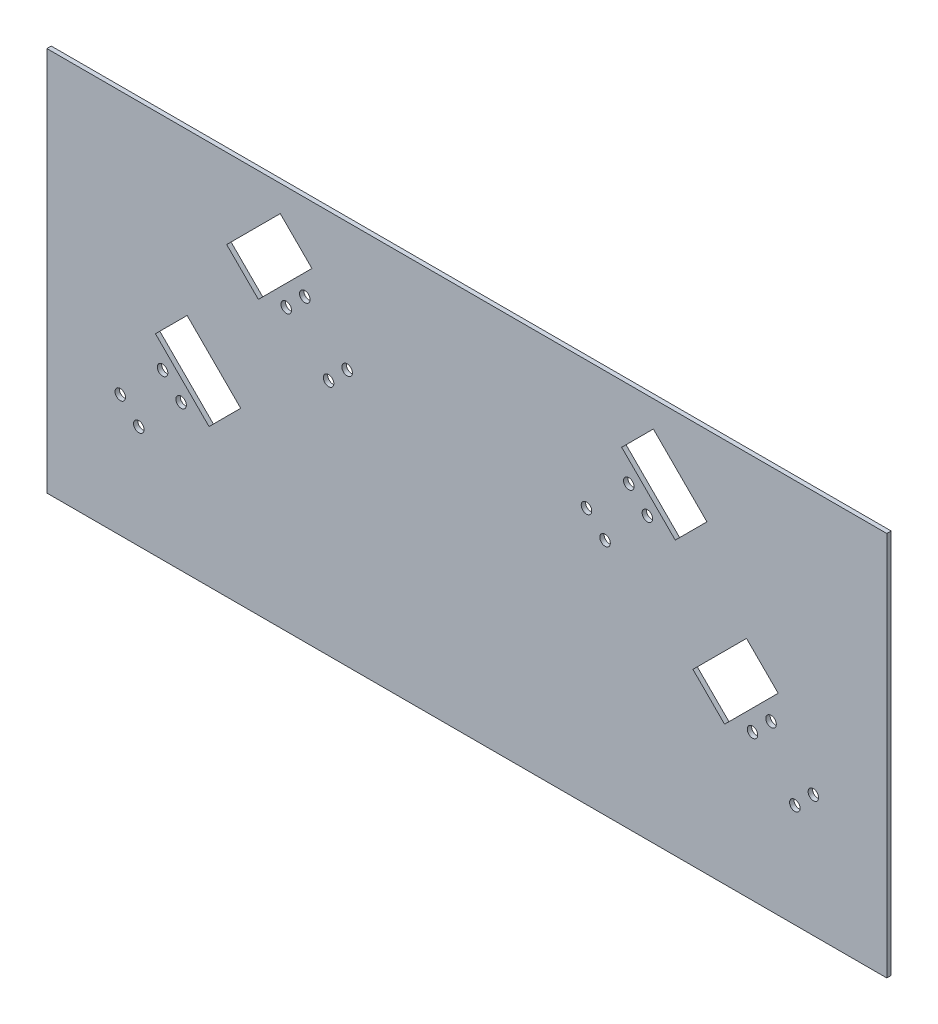
SolidWorks part; units mm, degrees
ref_plane "Front" through (0, 0, 0) normal (0, 0, 1) x (1, 0, 0)
ref_plane "Top" through (0, 0, 0) normal (0, 1, 0) x (1, 0, 0)
ref_plane "Right" through (0, 0, 0) normal (1, 0, 0) x (0, 0, -1)
sketch "Sketch1" plane through (0, 0, 0) normal (0, 0, 1) x (1, 0, 0)
  line L0 (0, -42.031) -> (0, 0) construction
  line L1 (-101.6, 0) -> (101.6, 0)
  line L13 (-206.5277, -159.2953) -> (-183.5467, -136.3143) construction
  line L31 (-304.8, 0) -> (304.8, 0)
  line L32 (-304.8, 0) -> (-304.8, -279.4)
  line L33 (-304.8, -279.4) -> (304.8, -279.4)
  line L34 (304.8, 0) -> (304.8, -279.4)
  line L51 (-116.131, -50.2511) -> (-47.7374, -118.6447)
  line L52 (-116.131, -50.2511) -> (-143.0718, -77.1919)
  line L53 (-143.0718, -77.1919) -> (-74.6782, -145.5855)
  line L54 (-47.7374, -118.6447) -> (-74.6782, -145.5855)
  line L55 (-154.8274, -38.4954) -> (-131.8465, -61.4764) construction
  line L56 (-129.6014, -63.7215) -> (-61.2078, -132.1151) construction
  line L57 (-195.3024, -175.0107) -> (-222.2432, -148.07)
  line L58 (-195.3024, -175.0107) -> (-263.696, -243.4044)
  line L59 (-263.696, -243.4044) -> (-290.6368, -216.4636)
  line L60 (-222.2432, -148.07) -> (-290.6368, -216.4636)
  line L61 (-208.7728, -161.5403) -> (-277.1664, -229.934) construction
  line L62 (-263.5523, -189.3791) -> (-235.6776, -217.2539)
  line L63 (-242.8977, -168.7245) -> (-215.957, -195.6653) construction
  line L69 (-101.7626, -118.501) -> (-74.8218, -91.5603)
  line L70 (-95.4764, -70.9057) -> (-122.4172, -97.8464) construction
  line L71 (95.4764, -70.9057) -> (122.4172, -97.8464) construction
  line L72 (242.8977, -168.7245) -> (215.957, -195.6653) construction
  line L73 (208.7728, -161.5403) -> (277.1664, -229.934) construction
  line L74 (129.6014, -63.7215) -> (61.2078, -132.1151) construction
  line L75 (154.8274, -38.4954) -> (131.8465, -61.4764) construction
  line L76 (206.5277, -159.2953) -> (183.5467, -136.3143) construction
  line L77 (101.7626, -118.501) -> (74.8218, -91.5603)
  line L78 (263.5523, -189.3791) -> (235.6776, -217.2539)
  line L79 (222.2432, -148.07) -> (290.6368, -216.4636)
  line L80 (263.696, -243.4044) -> (290.6368, -216.4636)
  line L81 (195.3024, -175.0107) -> (263.696, -243.4044)
  line L82 (195.3024, -175.0107) -> (222.2432, -148.07)
  line L83 (47.7374, -118.6447) -> (74.6782, -145.5855)
  line L84 (143.0718, -77.1919) -> (74.6782, -145.5855)
  line L85 (116.131, -50.2511) -> (143.0718, -77.1919)
  line L86 (116.131, -50.2511) -> (47.7374, -118.6447)
  circle A0 centre (-220.8063, -160.1035) radius 3.81
  circle A1 centre (-207.3359, -173.5739) radius 3.81
  circle A2 centre (-238.0484, -204.2864) radius 3.81
  circle A3 centre (-251.5188, -190.816) radius 3.81
  circle A4 centre (-131.0382, -75.755) radius 3.8222
  circle A5 centre (-117.5679, -62.2846) radius 3.8222
  circle A6 centre (-86.8554, -92.9971) radius 3.8222
  circle A7 centre (-100.3258, -106.4675) radius 3.8222
  circle A8 centre (100.3258, -106.4675) radius 3.8222
  circle A9 centre (86.8554, -92.9971) radius 3.8222
  circle A10 centre (117.5679, -62.2846) radius 3.8222
  circle A11 centre (131.0382, -75.755) radius 3.8222
  circle A12 centre (251.5188, -190.816) radius 3.81
  circle A13 centre (238.0484, -204.2864) radius 3.81
  circle A14 centre (207.3359, -173.5739) radius 3.81
  circle A15 centre (220.8063, -160.1035) radius 3.81
  point P22 (0, 0)
  line B0 (-135.382, -19.05) -> (-174.2729, -57.9409)
  line B1 (-135.382, -19.05) -> (-112.401, -42.031)
  line B2 (-112.401, -42.031) -> (-151.2919, -80.9218)
  line B3 (-174.2729, -57.9409) -> (-151.2919, -80.9218)
  line B4 (-225.9731, -139.8498) -> (-187.0823, -178.7407)
  line B5 (-225.9731, -139.8498) -> (-202.9922, -116.8689)
  line B6 (-202.9922, -116.8689) -> (-164.1013, -155.7597)
  line B7 (-187.0823, -178.7407) -> (-164.1013, -155.7597)
  line B8 (225.9731, -139.8498) -> (187.0823, -178.7407)
  line B9 (225.9731, -139.8498) -> (202.9922, -116.8689)
  line B10 (202.9922, -116.8689) -> (164.1013, -155.7597)
  line B11 (187.0823, -178.7407) -> (164.1013, -155.7597)
  line B12 (135.382, -19.05) -> (174.2729, -57.9409)
  line B13 (135.382, -19.05) -> (112.401, -42.031)
  line B14 (112.401, -42.031) -> (151.2919, -80.9218)
  line B15 (174.2729, -57.9409) -> (151.2919, -80.9218)
  dimension "D14" = 7.62
  dimension "D2" = 203.2
  dimension "D3" = 609.6
  dimension "D9" = 279.4
  dimension "D1" = 96.7232
  dimension "D4" = 38.1
  dimension "D5" = 45
  dimension "D8" = 96.7232
  dimension "D10" = 38.1
  dimension "D12" = 19.05
  dimension "D13" = 58.928
  dimension "D7" = 61.976
  dimension "D6" = 3.175
  dimension "D11" = 58.42
  dimension "D15" = 9.525
  dimension "D16" = 50.927
  dimension "D17" = 29.21
  dimension "D18" = 58.42
  dimension "D19" = 29.21
  dimension "D20" = 9.525
  dimension "D21" = 50.927
  dimension "D22" = 135.382
  dimension "D23" = 3.175
sketch_block_instance "Block1-1"
sketch_block "Block1" parameters "D1"=55, "D2"=32.5
sketch_block_instance "Block1-2"
sketch_block_instance "Block1-5"
sketch_block_instance "Block1-6" parameters "D14"=5.651, "D1"=105.4961, "D2"=82.55, "D3"=288.4146, "D4"=12.4794, "D5"=91.1388, "D6"=8.987, "D7"=33.3267, "D8"=50.8, "D9"=76.2, "D10"=67.5967, "D11"=120.1947, "D12"=103.2688, "D13"=147.2186, "D15"=7.9375, "D16"=39.4209, "D17"=26.9408, "D18"=38.1, "D19"=38.1, "D20"=9.525, "D21"=9.525, "D22"=143.6831, "D23"=44.704
ref_plane "Plane1" through (-58.166, 58.166, 0) normal (0.7071, -0.7071, 0) x (0, 0, 1)
ref_plane "Plane2" through (-182.9115, -182.9115, 0) normal (0.7071, 0.7071, 0) x (0, 0, -1)
extrude "Boss-Extrude1" add sketch "Sketch1" against normal blind 3.175 contours L32 L33 L34 L31
extrude "Cut-Extrude1" cut sketch "Sketch1<9>" against normal through all contours B0 B3 B2 B1 | B4 B7 B6 B5 | B15 B12 B13 B14 | B11 B8 B9 B10 | A4 | A7 | A2 | A1 | A5 | A6 | A0 | A3 region at (-143.337, -49.9859, 0) region at (-195.0372, -147.8048, 0) region at (195.0372, -147.8048, 0) region at (143.337, -49.9859, 0)
sketch "Sketch1<9>" plane through (0, 0, 0) normal (0, 0, 1) x (1, 0, 0) same geometry as "Sketch1"
extrude "Cut-Extrude2" cut sketch "Sketch1<10>" against normal through all contours A11 | A10 | A9 | A8 | A13 | A12 | A15 | A14 region at (100.3258, -106.4675, 0) region at (86.8554, -92.9971, 0) region at (117.5679, -62.2846, 0) region at (131.0382, -75.755, 0) region at (251.5188, -190.816, 0) region at (238.0484, -204.2864, 0) region at (207.3359, -173.5739, 0) region at (220.8063, -160.1035, 0)
sketch "Sketch1<10>" plane through (0, 0, 0) normal (0, 0, 1) x (1, 0, 0) same geometry as "Sketch1"
